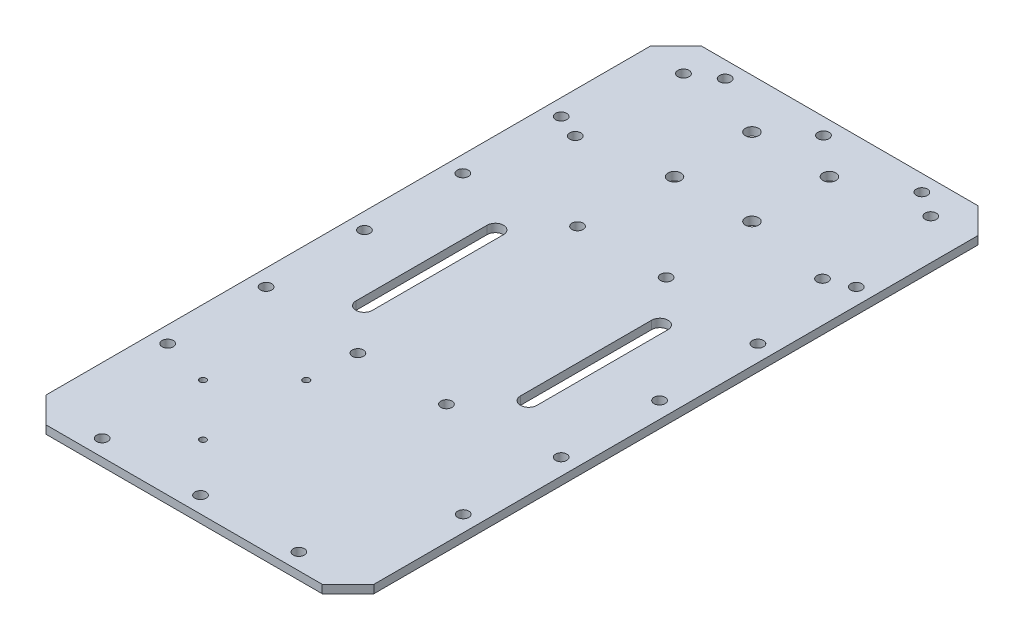
SolidWorks part; units mm, degrees
ref_plane "Front Plane" through (0, 0, 0) normal (0, 0, 1) x (1, 0, 0)
ref_plane "Top Plane" through (0, 0, 0) normal (0, 1, 0) x (1, 0, 0)
ref_plane "Right Plane" through (0, 0, 0) normal (1, 0, 0) x (0, 0, -1)
sketch "Sketch2" plane through (0, 0, 0) normal (0, 1, 0) x (1, 0, 0)
  line L0 (0, 10) -> (0, 244)
  line L1 (10, 254) -> (117, 254)
  line L2 (127, 244) -> (127, 10)
  line L3 (117, 0) -> (10, 0)
  line L4 (0, 244) -> (10, 254)
  line L5 (117, 254) -> (127, 244)
  line L6 (127, 10) -> (117, 0)
  line L7 (10, 0) -> (0, 10)
  line L8 (63.5, 254) -> (63.5, 243.84) construction
  line L9 (15.621, 241.3) -> (15.621, 199.39) construction
  line L10 (0, 127) -> (127, 127) construction
  line L11 (63.5, 243.84) -> (63.5, 199.39) construction
  line L12 (15.621, 199.39) -> (111.379, 199.39) construction
  line L13 (111.379, 199.39) -> (111.379, 241.3) construction
  line L14 (111.379, 241.3) -> (15.621, 241.3) construction
  line L15 (63.5, 127) -> (46.355, 127) construction
  line L16 (46.355, 127) -> (46.355, 169.545) construction
  line L17 (46.355, 169.545) -> (80.645, 169.545) construction
  line L18 (80.645, 169.545) -> (80.645, 84.455) construction
  line L19 (80.645, 84.455) -> (46.355, 84.455) construction
  line L20 (46.355, 84.455) -> (46.355, 127) construction
  line L21 (63.5, 127) -> (92.202, 127)
  line L27 (34.8088, 101.6) -> (34.8088, 114.3)
  line L29 (28.4588, 139.7) -> (28.4588, 101.6)
  line L31 (34.8088, 114.3) -> (34.8088, 139.7)
  line L34 (48.5, 205.9228) -> (48.5, 234.95) construction
  line L35 (48.5, 234.95) -> (78.5, 234.95) construction
  line L36 (78.5, 234.95) -> (78.5, 204.9501) construction
  line L37 (78.5, 204.9501) -> (48.5, 204.9501) construction
  line L38 (48.5, 204.9501) -> (48.5, 205.9228) construction
  line L43 (31.6338, 152.4) -> (31.6338, 101.6) construction
  line L44 (34.8088, 152.4) -> (34.8088, 101.6)
  line L45 (28.4588, 152.4) -> (28.4588, 101.6)
  line L46 (63.5, 0) -> (63.5, 254) construction
  line L47 (95.3662, 152.4) -> (95.3662, 101.6) construction
  line L48 (92.1912, 152.4) -> (92.1912, 101.6)
  line L49 (98.5412, 152.4) -> (98.5412, 101.6)
  circle A0 centre (6.35, 88.9) radius 2.159
  circle A1 centre (6.35, 165.1) radius 2.159
  circle A2 centre (120.65, 165.1) radius 2.159
  circle A3 centre (120.81, 50.8) radius 2.159
  circle A4 centre (6.35, 50.8) radius 2.159
  circle A13 centre (25.4, 247.65) radius 2.159
  circle A14 centre (101.6, 247.65) radius 2.159
  circle A15 centre (101.6, 6.35) radius 2.159
  circle A16 centre (25.4, 6.35) radius 2.159
  circle A17 centre (15.621, 241.3) radius 2.159
  circle A18 centre (15.621, 199.39) radius 2.159
  circle A19 centre (111.379, 199.39) radius 2.159
  circle A20 centre (111.379, 241.3) radius 2.159
  circle A22 centre (46.355, 169.545) radius 2.159
  circle A23 centre (46.355, 84.455) radius 2.159
  circle A24 centre (80.645, 84.455) radius 2.159
  circle A25 centre (80.645, 169.545) radius 2.159
  circle A26 centre (120.65, 88.9) radius 2.159
  circle A27 centre (48.5, 234.95) radius 2.54
  circle A30 centre (78.5, 234.95) radius 2.54
  circle A31 centre (78.5, 204.9501) radius 2.54
  circle A34 centre (48.5, 204.9501) radius 2.54
  circle A36 centre (120.65, 203.2) radius 2.159
  arc A38 (34.8088, 152.4) -> (28.4588, 152.4) centre (31.6338, 152.4) ccw
  arc A39 (28.4588, 101.6) -> (34.8088, 101.6) centre (31.6338, 101.6) ccw
  arc A40 (92.1912, 152.4) -> (98.5412, 152.4) centre (95.3662, 152.4) cw
  arc A41 (98.5412, 101.6) -> (92.1912, 101.6) centre (95.3662, 101.6) cw
  circle A42 centre (6.35, 203.2) radius 2.159
  circle A43 centre (63.5, 247.65) radius 2.159
  circle A44 centre (63.5, 6.35) radius 2.159
  circle A45 centre (120.65, 127) radius 2.159
  circle A46 centre (6.35, 127) radius 2.159
  circle A47 centre (25.4, 45.4) radius 1.25
  circle A48 centre (45.4, 65.4) radius 1.25
  circle A49 centre (45.4, 25.4) radius 1.25
  point P0 (0, 0)
  point P1 (0, 254)
  point P3 (127, 254)
  point P4 (127, 0)
  point P32 (31.6338, 127)
  point P73 (95.3662, 127)
  dimension "D1" = 12.7
  dimension "D2" = 254
  dimension "D8" = 6.35
  dimension "D9" = 6.35
  dimension "D10" = 38.1
  dimension "D11" = 38.1
  dimension "D13" = 38.1
  dimension "D14" = 38.1
  dimension "D16" = 6.35
  dimension "D17" = 6.35
  dimension "D18" = 6.35
  dimension "D20" = 38.1
  dimension "D21" = 6.35
  dimension "D22" = 6.35
  dimension "D23" = 6.35
  dimension "D24" = 38.1
  dimension "D25" = 29.9999
  dimension "D26" = 29.9999
  dimension "D27" = 5.08
  dimension "D28" = 5.08
  dimension "D29" = 5.08
  dimension "D30" = 38.1
  dimension "D31" = 6.35
  dimension "D32" = 4.318
  dimension "D33" = 4.318
  dimension "D34" = 4.318
  dimension "D35" = 4.318
  dimension "D36" = 4.318
  dimension "D37" = 4.318
  dimension "D38" = 4.318
  dimension "D39" = 4.318
  dimension "D40" = 20
  dimension "D41" = 40
  dimension "D42" = 20
  dimension "D43" = 2.5
  dimension "D44" = 4.318
  dimension "D45" = 6.35
  dimension "D46" = 4.318
  dimension "D47" = 6.35
  dimension "D48" = 4.318
  dimension "D49" = 6.35
  dimension "D50" = 4.318
  dimension "D51" = 6.35
  dimension "D55" = 4.318
  dimension "D56" = 4.318
  dimension "D57" = 2.5
  dimension "D58" = 4.318
  dimension "D59" = 2.5
  dimension "D60" = 25.4
  dimension "D7" = 127
  dimension "D12" = 38.1
  dimension "D15" = 38.1
  dimension "D19" = 25.4
  dimension "D52" = 19.05
  dimension "D53" = 34.29
  dimension "D54" = 85.09
  dimension "D61" = 25.4
extrude "Boss-Extrude1" add sketch "Sketch2" along normal blind 3.175 contours L7 L3 L6 L2 L5 L1 L4 L0 A46 A45 A44 A43 A42 A39 L29 L45 A38 L44 L31 L27 A34 A31 A26 A23 A22 A19 A18 A17 A14 A13 A4 A0 region at (63.5117, 0, -126.6181)
